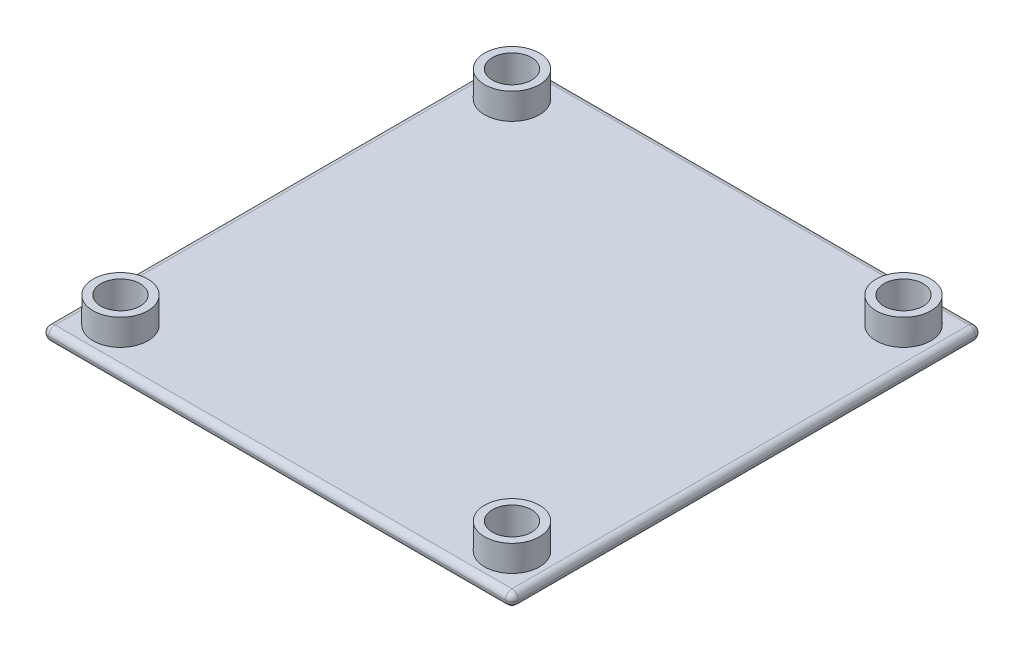
SolidWorks part; units mm, degrees
material "ABS"
ref_plane "Front Plane" through (0, 0, 0) normal (0, 0, 1) x (1, 0, 0)
ref_plane "Top Plane" through (0, 0, 0) normal (0, 1, 0) x (1, 0, 0)
ref_plane "Right Plane" through (0, 0, 0) normal (1, 0, 0) x (0, 0, -1)
sketch "Sketch2" plane through (0, 0, 0) normal (0, 1, 0) x (1, 0, 0)
  line L0 (0, 17.5) -> (0, 18) construction
  line L1 (-18, -18) -> (18, -18)
  line L2 (-18, -18) -> (-18, 18)
  line L3 (-18, 18) -> (18, 18)
  line L4 (18, -18) -> (18, 18)
  line L16 (0, 18) -> (0, 17.5) construction
  circle A0 centre (-15, 15) radius 1.5
  circle A1 centre (-15, -15) radius 1.5
  circle A2 centre (15, -15) radius 1.5
  circle A3 centre (15, 15) radius 1.5
  point P0 (0, 0)
  point P6 (0, 0)
  point P7 (0, 0)
  point P8 (0, 0)
  dimension "D5" = 3
  dimension "D6" = 3
  dimension "D7" = 3
  dimension "D8" = 3
  dimension "D1" = 36
  dimension "D2" = 36
  dimension "D3" = 30
extrude "Boss-Extrude2" add sketch "Sketch2" along normal blind 1
fillet "Fillet1" radius 0.5 8 edges at (0, 1, -18) (0, 0, -18) (18, 1, 0) (18, 0, 0) (-18, 1, 0) (-18, 0, 0) (0, 1, 18) (0, 0, 18)
sketch "Croquis1" plane through (0, 1, 0) normal (0, 1, 0) x (1, 0, 0)
  circle A0 centre (-15, -15) radius 1.5 construction
  circle A1 centre (-15, 15) radius 1.5 construction
  circle A2 centre (15, 15) radius 1.5 construction
  circle A3 centre (15, -15) radius 1.5 construction
  circle A4 centre (-15, -15) radius 1.5
  circle A5 centre (-15, 15) radius 1.5
  circle A6 centre (15, 15) radius 1.5
  circle A7 centre (15, -15) radius 1.5
  circle A8 centre (-15, -15) radius 2.1
  circle A9 centre (-15, 15) radius 2.1
  circle A10 centre (15, 15) radius 2.1
  circle A11 centre (15, -15) radius 2.1
  dimension "D1" = 0.6
extrude "Saliente-Extruir1" add sketch "Croquis1" along normal blind 2
